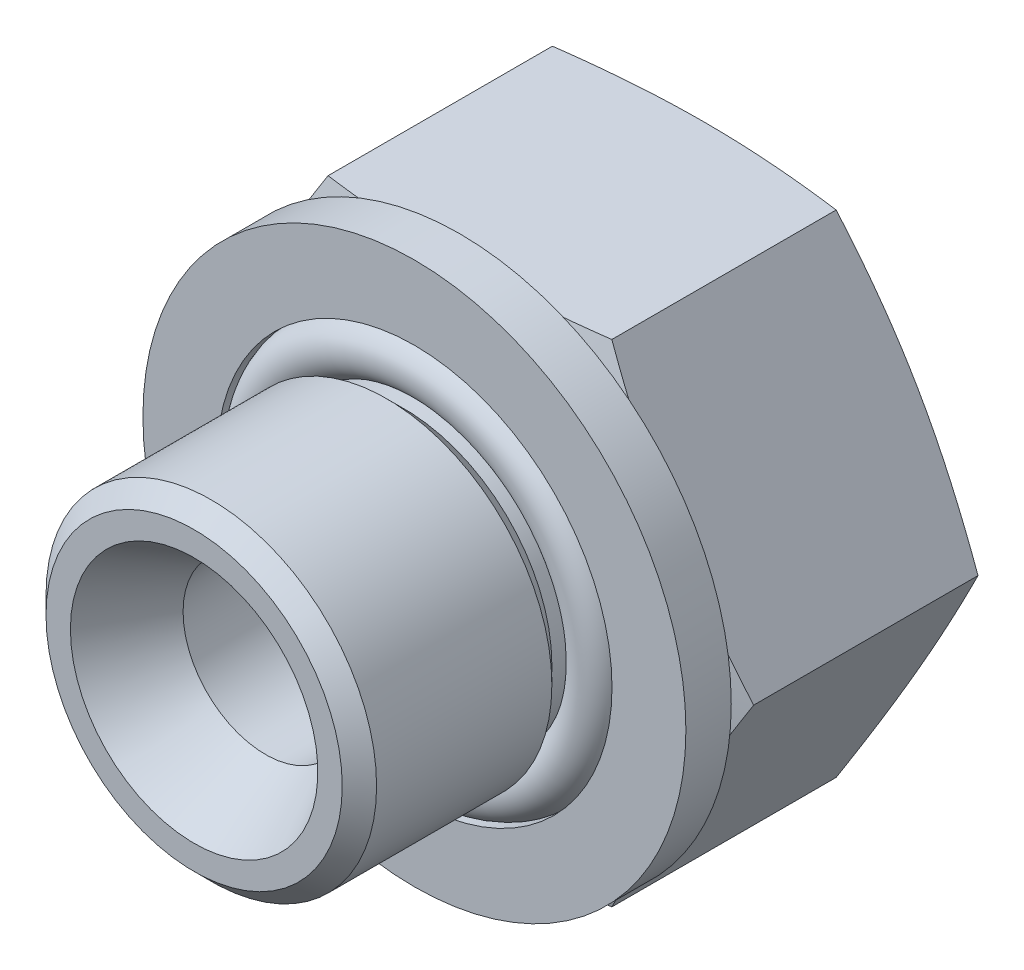
SolidWorks part; units mm, degrees
material "4140 H/T"
ref_plane "Front Plane" through (0, 0, 0) normal (0, 0, 1) x (1, 0, 0)
ref_plane "Top Plane" through (0, 0, 0) normal (0, 1, 0) x (1, 0, 0)
ref_plane "Right Plane" through (0, 0, 0) normal (1, 0, 0) x (0, 0, -1)
sketch "Sketch1" plane through (0, 0, 0) normal (1, 0, 0) x (0, 0, -1)
  line L0 (0, 0) -> (-60.3675, 0) construction
  line L1 (0, 0) -> (0, 7.15)
  line L2 (-0.3403, 8.42) -> (-6.7797, 8.42)
  line L3 (-7.12, 7.15) -> (-7.12, 4.3)
  line L4 (-9.25, 4.81) -> (-14.35, 4.81)
  line L5 (-14.85, 4.31) -> (-14.85, 3.6)
  line L6 (-14.85, 3.6) -> (-12.7715, 2.4)
  line L7 (-12.7715, 2.4) -> (-10.2921, 2.4)
  line L8 (-10.2921, 2.4) -> (-8.85, 0)
  line L9 (-14.35, 4.81) -> (-14.85, 4.31)
  line L10 (-7.12, 7.15) -> (-6.7797, 8.42)
  line L11 (0, 7.15) -> (-0.3403, 8.42)
  line L12 (0, 0) -> (-8.85, 0)
  line L13 (-9.25, 4.81) -> (-8.74, 4.3)
  line L14 (-8.74, 4.3) -> (-7.12, 4.3)
  point P7 (-14.85, 4.81)
  dimension "D1" = 16.84
  dimension "D2" = 9.62
  dimension "D3" = 7.12
  dimension "D4" = 14.85
  dimension "D5" = 4.8
  dimension "D6" = 30
  dimension "D7" = 7.2
  dimension "D8" = 59
  dimension "D9" = 6
  dimension "D10" = 15
  dimension "D11" = 15
  dimension "D13" = 14.3
  dimension "D14" = 5.6
  dimension "D15" = 8.6
  dimension "D16" = 45
revolve "Revolve1" add sketch "Sketch1" angle 360 about L0
cosmetic thread "Cosmetic Thread1" parameters "D2"=7.365
sketch "Sketch2" plane through (0, 0, 0) normal (0, 0, -1) x (-1, 0, 0)
  line L1 (-4.1281, 7.15) -> (-8.2561, 0)
  line L2 (-8.2561, 0) -> (-4.1281, -7.15)
  line L3 (-4.1281, -7.15) -> (4.1281, -7.15)
  line L4 (4.1281, -7.15) -> (8.2561, 0)
  line L5 (8.2561, 0) -> (4.1281, 7.15)
  line L6 (4.1281, 7.15) -> (-4.1281, 7.15)
  circle A0 centre (0, 0) radius 7.15 construction
  dimension "D1" = 14.3
extrude "Extrude2" cut sketch "Sketch2" against normal up to surface (7.12 mm away) flip side to cut up to face at (-4.3, 0, 7.12)
sketch "Sketch3" plane through (0, 0, 0) normal (0, 0, -1) x (-1, 0, 0)
  line L0 (-5.4003, 0) -> (5.278, 0) construction
  text T0 "S73-02" font "Century Gothic" height 2
extrude "Cut-Extrude1" cut sketch "Sketch3" against normal blind 0.01
sketch "Sketch4" plane through (0, 0, 0) normal (1, 0, 0) x (0, 0, -1)
  line L0 (0, 0) -> (-19.0597, 0) construction
  line L1 (-7.12, 7.15) -> (-7.12, 3.575) construction
  line L2 (-7.12, 5.75) -> (-8.44, 5.75)
  line L3 (-7.12, 5.75) -> (-7.12, 7.9)
  line L4 (-7.12, 7.9) -> (-8.44, 7.9)
  line L5 (-8.44, 5.75) -> (-8.44, 7.9)
  dimension "D1" = 1.32
  dimension "D2" = 15.8
  dimension "D3" = 11.5
revolve "Revolve2" add sketch "Sketch4" angle 360 about L0
sketch "Sketch5" plane through (0, 0, 0) normal (1, 0, 0) x (0, 0, -1)
  line L0 (-8.44, 7.9) -> (-8.44, -7.9) construction
  line L1 (0, 0) -> (-17.5984, 0) construction
  circle A0 centre (-7.94, 5) radius 0.765
  dimension "D1" = 0.5
  dimension "D2" = 1.53
  dimension "D3" = 10
revolve "Revolve3" add sketch "Sketch5" angle 360 about L1
